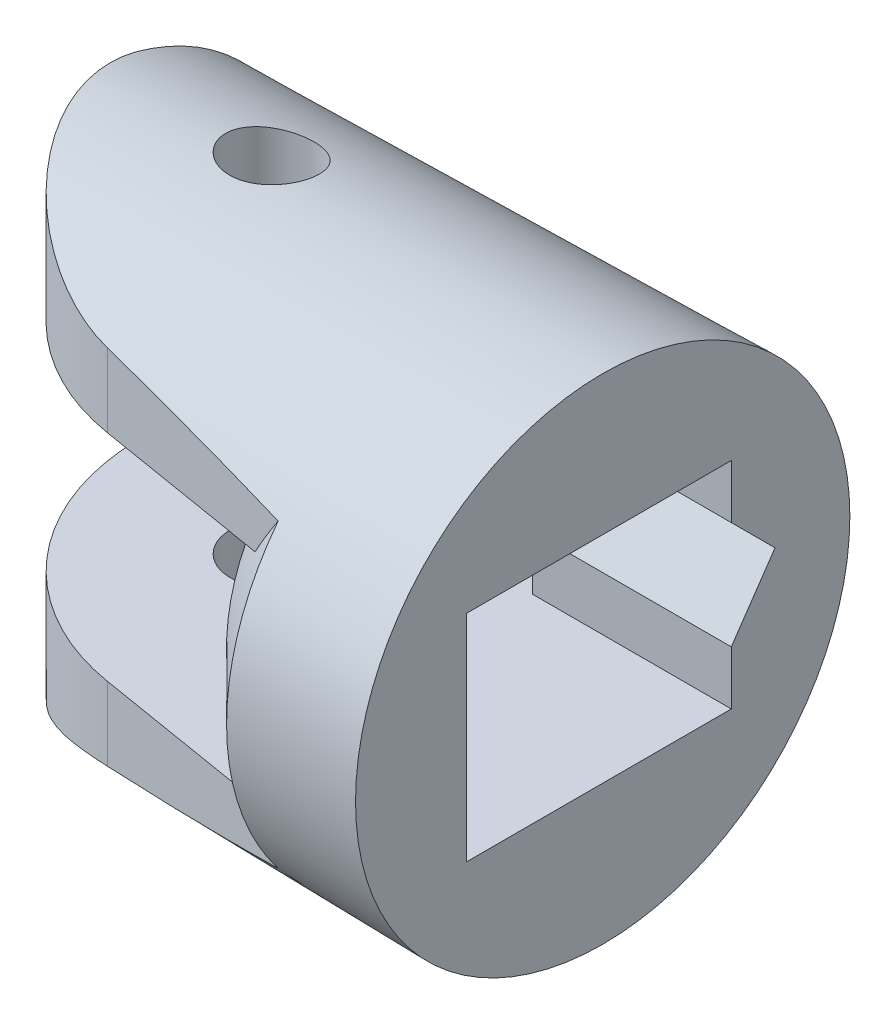
SolidWorks part; units mm, degrees
ref_plane "Ön Düzlem" through (0, 0, 0) normal (0, 0, 1) x (1, 0, 0)
ref_plane "Üst Düzlem" through (0, 0, 0) normal (0, 1, 0) x (1, 0, 0)
ref_plane "Sağ Düzlem" through (0, 0, 0) normal (1, 0, 0) x (0, 0, -1)
sketch "Sketch1" plane through (0, 0, 0) normal (1, 0, 0) x (0, 0, -1)
  circle A0 centre (0, 0) radius 7.5
  dimension "D1" = 15
extrude "Boss-Extrude1" add sketch "Sketch1" along normal blind 18
sketch "Sketch2" plane through (0, 0, 0) normal (0, 1, 0) x (1, 0, 0)
  line L0 (10, 5.5026) -> (0, 5.4873)
  line L1 (18, -7.5) -> (18, 7.5) construction
  line L2 (10, -5.5) -> (5.8546, -4.8143)
  line L3 (0, 5.4873) -> (0, 2.2976)
  line L5 (0, 7.5) -> (0, -7.5) construction
  line L6 (10, -5.5) -> (10, -11.2528)
  line L9 (10, -11.2528) -> (-2.5986, -11.2528)
  line L10 (-2.5986, -11.2528) -> (-2.5986, 9.735)
  line L11 (-2.5986, 9.735) -> (10, 9.735)
  line L12 (10, 9.735) -> (10, 5.5026)
  arc A0 (0, 2.2976) -> (5.8546, -4.8143) centre (6.997, 2.0919) ccw
  dimension "D2" = 7
  dimension "D1" = 8
  dimension "D3" = 11.0026
  dimension "D4" = 8
  dimension "D5" = 2
extrude "Cut-Extrude1" cut sketch "Sketch2" against normal blind 18 and the other way blind 18 contours L11 L12 L0 L3 A0 L2 L6 L9 L10
sketch "Sketch4" plane through (0, 0, 0) normal (0, 1, 0) x (1, 0, 0)
  line L0 (10, 5.5026) -> (-1.0009, 5.5026)
  line L1 (10, -5.5) -> (-1.0009, -5.5)
  line L2 (-1.0009, -5.5) -> (-1.0009, 5.5026)
  line L3 (10, 5.5026) -> (10, -5.5)
extrude "Cut-Extrude3" cut sketch "Sketch4" against normal blind 3.25 and the other way blind 3.25
sketch "Sketch5" plane through (0, 0, 0) normal (0, 1, 0) x (1, 0, 0)
  line L0 (18, 7.5) -> (18, 1) construction
  line L1 (18, -7.5) -> (18, 7.5) construction
  line L2 (18, 1) -> (5, 1) construction
  circle A0 centre (5, 1) radius 1.25
  dimension "D3" = 2.5
  dimension "D2" = 13
  dimension "D1" = 6.5
extrude "Cut-Extrude4" cut sketch "Sketch5" against normal through all and the other way through all
sketch "Sketch6" plane through (18, 0, 0) normal (1, 0, 0) x (0, 0, -1)
  circle A0 centre (0, 0) radius 7.5 construction
  circle A1 centre (0, 0) radius 7.5
extrude "Cut-Extrude-Thin2" cut sketch "Sketch6" against normal blind 23.25 draft 1 thin draft outward yes thin type one direction wall 10
fillet "Fillet1" radius 0.5 2 edges at (0, -3.9448, -5.4873) (0, 3.9448, -5.4873)
sketch "Sketch7" plane through (0, 0, 0) normal (0, 1, 0) x (1, 0, 0)
  line L1 (18, 7.5) -> (16, 7.5)
  line L2 (18, 7.5) -> (18, -7.6621)
  line L3 (18, -7.6621) -> (16, -7.6621)
  line L4 (16, 7.5) -> (16, -7.6621)
  dimension "D1" = 2
extrude "Cut-Extrude5" cut sketch "Sketch7" against normal blind 23.25 and the other way blind 23.25
chamfer "Chamfer1" distance 2 angle 45 1 edges at (10, 0, 7.3604) first distance on face at (10, 0, -0.001)
chamfer "Chamfer2" distance 1 angle 45 1 edges at (10, 0, -7.3604) first distance on face at (10, 0, -2.3742)
sketch "Sketch8" plane through (16, 0, 0) normal (1, 0, 0) x (0, 0, -1)
  line L0 (0, 0) -> (-4.1162, 0) construction
  line L1 (-4.1162, 0) -> (3.8838, 0) construction
  line L2 (3.8838, 0) -> (3.8838, 3.25) construction
  line L3 (3.8838, 3.25) -> (-4.1162, 3.25) construction
  line L4 (-4.1162, 3.25) -> (-4.1162, -3.25) construction
  line L5 (-4.1162, -3.25) -> (3.8838, -3.25) construction
  line L6 (3.8838, -3.25) -> (3.8838, 0) construction
  line L7 (3.8838, 1.625) -> (5.2049, 0.3038)
  line L8 (5.2049, 0.3038) -> (3.8838, -1.625)
  line L9 (3.8838, -1.625) -> (3.8838, -3.25)
  line L10 (3.8838, -3.25) -> (-4.1162, -3.25)
  line L11 (-4.1162, -3.25) -> (-4.1162, 3.25)
  line L12 (-4.1162, 3.25) -> (3.8838, 3.25)
  line L13 (3.8838, 3.25) -> (3.8838, 1.625)
  dimension "D1" = 6.5
  dimension "D2" = 3.25
  dimension "D3" = 8
  dimension "D4" = 1.625
  dimension "D5" = 100.591
  dimension "D6" = 1.625
extrude "Cut-Extrude6" cut sketch "Sketch8" against normal blind 10
